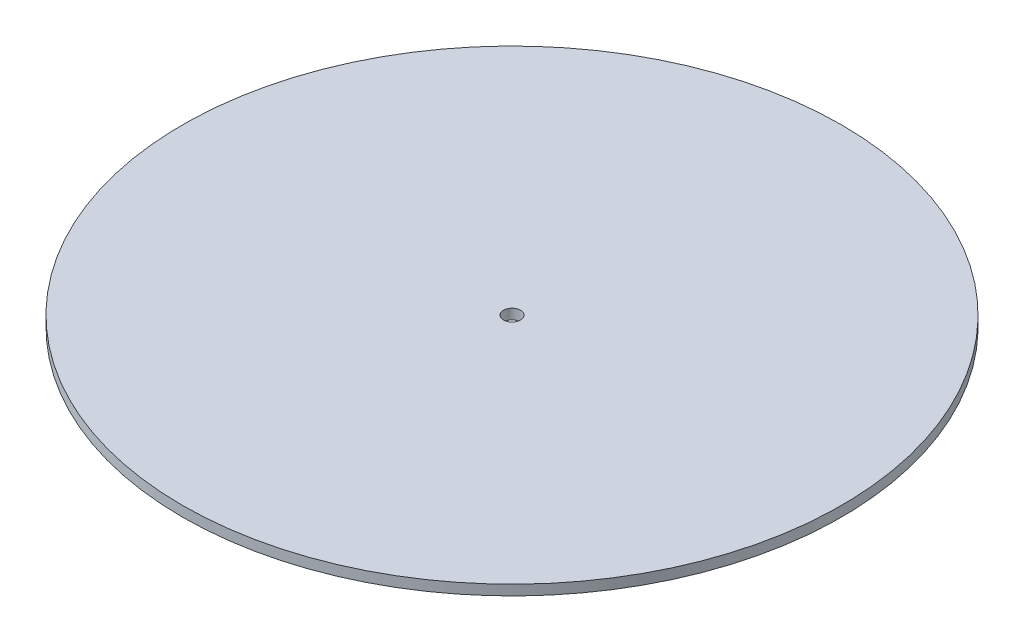
SolidWorks part; units mm, degrees
ref_plane "Front Plane" through (0, 0, 0) normal (0, 0, 1) x (1, 0, 0)
ref_plane "Top Plane" through (0, 0, 0) normal (0, 1, 0) x (1, 0, 0)
ref_plane "Right Plane" through (0, 0, 0) normal (1, 0, 0) x (0, 0, -1)
ref_axis "Axe1" through (0, 55, 0) along (0, -1, 0)
sketch "Esquisse2" plane through (0, 0, 0) normal (0, 0, 1) x (1, 0, 0)
  line L0 (0, 0) -> (97, 0)
  line L1 (97, 0) -> (97, 3)
  line L4 (97, 3) -> (0, 3)
  line L5 (0, 55) -> (0, -55) construction
  line L6 (0, 3) -> (0, 0)
  dimension "D1" = 97
  dimension "D3" = 3
revolve "Révolution1" add sketch "Esquisse2" angle 360 about axis through (0, 55, 0) along (0, -1, 0)
sketch "Esquisse4" plane through (0, 3, 0) normal (0, 1, 0) x (1, 0, 0)
  circle A0 centre (0, 0) radius 2.5
  dimension "D1" = 5
extrude "Enlèv. mat.-Extru.6" cut sketch "Esquisse4" against normal through all
